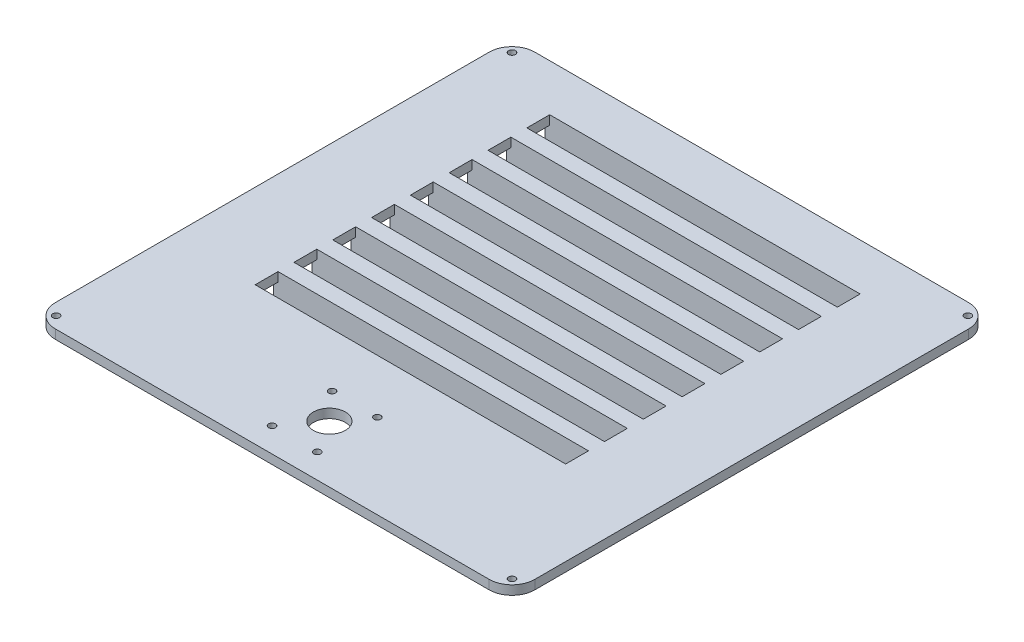
SolidWorks part; units mm, degrees
ref_plane "Front Plane" through (0, 0, 0) normal (0, 0, 1) x (1, 0, 0)
ref_plane "Top Plane" through (0, 0, 0) normal (0, 1, 0) x (1, 0, 0)
ref_plane "Right Plane" through (0, 0, 0) normal (1, 0, 0) x (0, 0, -1)
sketch "Sketch1" plane through (0, 0, 0) normal (0, 1, 0) x (1, 0, 0)
  line L0 (-101, -101) -> (-101, 101)
  line L5 (-105, -105) -> (105, -105)
  line L6 (-105, -105) -> (-105, 105)
  line L7 (-105, 105) -> (105, 105)
  line L8 (105, -105) -> (105, 105)
  line L9 (-101, 101) -> (101, 101)
  line L10 (101, -101) -> (101, 101)
  line L11 (-101, -101) -> (101, -101)
  line L12 (-101, 101) -> (-99.8333, 99.8333) construction
  line L13 (-55, 0) -> (55, 0) construction
  line L14 (-101, -101) -> (-99.8333, -99.8333) construction
  line L15 (0, -55) -> (0, 55) construction
  line L16 (101, -101) -> (99.8333, -99.8333) construction
  line L17 (101, 101) -> (99.8333, 99.8333) construction
  circle A1 centre (-99.8333, 99.8333) radius 1.5
  circle A2 centre (-99.8333, -99.8333) radius 1.5
  circle A3 centre (99.8333, -99.8333) radius 1.5
  circle A4 centre (99.8333, 99.8333) radius 1.5
  point P0 (0, 0)
  point P6 (-105, 0)
  point P7 (0, 105)
  dimension "D3" = 4
  dimension "D4" = 3
  dimension "D1" = 210
  dimension "D2" = 210
  dimension "D5" = 1.65
  dimension "D6" = 45
extrude "MainExtrude" add sketch "Sketch1" along normal blind 4 contours L6 L5 L8 L7
extrude "ScrewHoles" cut sketch "Sketch1<6>" along normal up to surface (4 mm away) contours A1 | A2 | A3 | A4 up to face at (0, 4, 0)
sketch "Sketch1<6>" plane through (0, 0, 0) normal (0, 1, 0) x (1, 0, 0) same geometry as "Sketch1"
fillet "RoundedCorners" radius 10 4 edges at (-105, 2, -105) (-105, 2, 105) (105, 2, -105) (105, 2, 105)
sketch "Sketch3" plane through (0, 0, 0) normal (0, 1, 0) x (1, 0, 0)
  line L145 (-68, 96.5) -> (68, 96.5) construction
  line L146 (-68, 96.5) -> (-68, -56.5) construction
  line L147 (-68, -56.5) -> (68, -56.5) construction
  line L148 (68, 96.5) -> (68, -56.5) construction
  line L149 (-68, 96.5) -> (68, -56.5) construction
  line L151 (68, 96.5) -> (-68, -56.5) construction
  line L152 (-68, 79.5) -> (68, 79.5) construction
  line L154 (-68, 62.5) -> (68, 62.5) construction
  line L155 (-68, 45.5) -> (68, 45.5) construction
  line L157 (-68, 28.5) -> (68, 28.5) construction
  line L158 (-68, 11.5) -> (68, 11.5) construction
  line L159 (-68, -5.5) -> (68, -5.5) construction
  line L160 (-68, -22.5) -> (68, -22.5) construction
  line L161 (-68, -39.5) -> (68, -39.5) construction
  line L162 (-68, 74.5) -> (68, 74.5)
  line L163 (-68, 57.5) -> (68, 57.5)
  line L164 (-68, 40.5) -> (68, 40.5)
  line L165 (-68, 23.5) -> (68, 23.5)
  line L166 (-68, 6.5) -> (68, 6.5)
  line L167 (-68, -10.5) -> (68, -10.5)
  line L168 (-68, -27.5) -> (68, -27.5)
  line L169 (-68, -44.5) -> (68, -44.5)
  line L170 (-68, 84.5) -> (68, 84.5)
  line L171 (-68, 67.5) -> (68, 67.5)
  line L172 (-68, 50.5) -> (68, 50.5)
  line L173 (-68, 33.5) -> (68, 33.5)
  line L174 (-68, 16.5) -> (68, 16.5)
  line L175 (-68, -0.5) -> (68, -0.5)
  line L176 (-68, -17.5) -> (68, -17.5)
  line L177 (-68, -34.5) -> (68, -34.5)
  line L178 (-68, 74.5) -> (-68, 84.5)
  line L179 (68, 74.5) -> (68, 84.5)
  line L180 (-68, 57.5) -> (-68, 67.5)
  line L181 (68, 57.5) -> (68, 67.5)
  line L182 (-68, 40.5) -> (-68, 50.5)
  line L183 (68, 40.5) -> (68, 50.5)
  line L184 (-68, 23.5) -> (-68, 33.5)
  line L185 (68, 23.5) -> (68, 33.5)
  line L186 (-68, 6.5) -> (-68, 16.5)
  line L187 (68, 6.5) -> (68, 16.5)
  line L188 (-68, -10.5) -> (-68, -0.5)
  line L189 (68, -10.5) -> (68, -0.5)
  line L190 (-68, -27.5) -> (-68, -17.5)
  line L191 (68, -27.5) -> (68, -17.5)
  line L192 (-68, -44.5) -> (-68, -34.5)
  line L193 (68, -44.5) -> (68, -34.5)
  line L200 (-10.8, -68) -> (-10.8, -94.3) construction
  line L201 (-95, -105) -> (95, -105) construction
  line L207 (-97.2358, 20) -> (95.5763, 20) construction
  line L208 (-10.8, -68) -> (9, -68) construction
  circle A0 centre (0, -80) radius 7
  circle A1 centre (-10.8, -68) radius 1.5
  circle A2 centre (-10.8, -94.3) radius 1.5
  circle A3 centre (9, -94.3) radius 1.5
  circle A4 centre (9, -68) radius 1.5
  point P70 (0, 20)
  dimension "D18" = 14
  dimension "D19" = 25
  dimension "D21" = 35.5
  dimension "D25" = 3
  dimension "D26" = 3
  dimension "D27" = 19.8
  dimension "D15" = 10.8
  dimension "D16" = 12
  dimension "D1" = 136
  dimension "D2" = 153
  dimension "D3" = 17
  dimension "D4" = 17
  dimension "D5" = 17
  dimension "D6" = 17
  dimension "D7" = 17
  dimension "D8" = 17
  dimension "D9" = 17
  dimension "D11" = 17
  dimension "D13" = 5
  dimension "D14" = 129
  dimension "D10" = 17
  dimension "D12" = 5
  dimension "D17" = 9
  dimension "D20" = 20
  dimension "D22" = 14.3
  dimension "D28" = 26.3
extrude "Trench" cut sketch "Sketch3" along normal blind 10
sketch "Sketch4" plane through (0, 0, 0) normal (0, 1, 0) x (1, 0, 0)
  line L0 (68, -34.5) -> (68, -44.5) construction
  line L1 (68, -44.5) -> (-68, -44.5) construction
  line L2 (-68, -44.5) -> (-68, -34.5) construction
  line L3 (-68, -34.5) -> (68, -34.5) construction
  line L4 (68, -17.5) -> (68, -27.5) construction
  line L5 (68, -27.5) -> (-68, -27.5) construction
  line L6 (-68, -27.5) -> (-68, -17.5) construction
  line L7 (-68, -17.5) -> (68, -17.5) construction
  line L8 (68, -0.5) -> (68, -10.5) construction
  line L9 (68, -10.5) -> (-68, -10.5) construction
  line L10 (-68, -10.5) -> (-68, -0.5) construction
  line L11 (-68, -0.5) -> (68, -0.5) construction
  line L12 (68, 16.5) -> (68, 6.5) construction
  line L13 (68, 6.5) -> (-68, 6.5) construction
  line L14 (-68, 6.5) -> (-68, 16.5) construction
  line L15 (-68, 16.5) -> (68, 16.5) construction
  line L16 (68, 33.5) -> (68, 23.5) construction
  line L17 (68, 23.5) -> (-68, 23.5) construction
  line L18 (-68, 23.5) -> (-68, 33.5) construction
  line L19 (-68, 33.5) -> (68, 33.5) construction
  line L20 (68, 50.5) -> (68, 40.5) construction
  line L21 (68, 40.5) -> (-68, 40.5) construction
  line L22 (-68, 40.5) -> (-68, 50.5) construction
  line L23 (-68, 50.5) -> (68, 50.5) construction
  line L24 (68, 67.5) -> (68, 57.5) construction
  line L25 (68, 57.5) -> (-68, 57.5) construction
  line L26 (-68, 57.5) -> (-68, 67.5) construction
  line L27 (-68, 67.5) -> (68, 67.5) construction
  line L28 (68, 84.5) -> (68, 74.5) construction
  line L29 (68, 74.5) -> (-68, 74.5) construction
  line L30 (-68, 74.5) -> (-68, 84.5) construction
  line L31 (-68, 84.5) -> (68, 84.5) construction
  line L32 (68, -34.5) -> (68, -44.5)
  line L33 (68, -44.5) -> (-68, -44.5)
  line L34 (-68, -44.5) -> (-68, -34.5)
  line L35 (-68, -34.5) -> (68, -34.5)
  line L36 (68, -17.5) -> (68, -27.5)
  line L37 (68, -27.5) -> (-68, -27.5)
  line L38 (-68, -27.5) -> (-68, -17.5)
  line L39 (-68, -17.5) -> (68, -17.5)
  line L40 (68, -0.5) -> (68, -10.5)
  line L41 (68, -10.5) -> (-68, -10.5)
  line L42 (-68, -10.5) -> (-68, -0.5)
  line L43 (-68, -0.5) -> (68, -0.5)
  line L44 (68, 16.5) -> (68, 6.5)
  line L45 (68, 6.5) -> (-68, 6.5)
  line L46 (-68, 6.5) -> (-68, 16.5)
  line L47 (-68, 16.5) -> (68, 16.5)
  line L48 (68, 33.5) -> (68, 23.5)
  line L49 (68, 23.5) -> (-68, 23.5)
  line L50 (-68, 23.5) -> (-68, 33.5)
  line L51 (-68, 33.5) -> (68, 33.5)
  line L52 (68, 50.5) -> (68, 40.5)
  line L53 (68, 40.5) -> (-68, 40.5)
  line L54 (-68, 40.5) -> (-68, 50.5)
  line L55 (-68, 50.5) -> (68, 50.5)
  line L56 (68, 67.5) -> (68, 57.5)
  line L57 (68, 57.5) -> (-68, 57.5)
  line L58 (-68, 57.5) -> (-68, 67.5)
  line L59 (-68, 67.5) -> (68, 67.5)
  line L60 (68, 84.5) -> (68, 74.5)
  line L61 (68, 74.5) -> (-68, 74.5)
  line L62 (-68, 74.5) -> (-68, 84.5)
  line L63 (-68, 84.5) -> (68, 84.5)
  line L64 (70, 86.5) -> (70, 72.5)
  line L65 (70, 72.5) -> (-70, 72.5)
  line L66 (-70, 72.5) -> (-70, 86.5)
  line L67 (-70, 86.5) -> (70, 86.5)
  line L68 (70, 69.5) -> (70, 55.5)
  line L69 (70, 55.5) -> (-70, 55.5)
  line L70 (-70, 55.5) -> (-70, 69.5)
  line L71 (-70, 69.5) -> (70, 69.5)
  line L72 (70, 52.5) -> (70, 38.5)
  line L73 (70, 38.5) -> (-70, 38.5)
  line L74 (-70, 38.5) -> (-70, 52.5)
  line L75 (-70, 52.5) -> (70, 52.5)
  line L76 (70, 35.5) -> (70, 21.5)
  line L77 (70, 21.5) -> (-70, 21.5)
  line L78 (-70, 21.5) -> (-70, 35.5)
  line L79 (-70, 35.5) -> (70, 35.5)
  line L80 (70, 18.5) -> (70, 4.5)
  line L81 (70, 4.5) -> (-70, 4.5)
  line L82 (-70, 4.5) -> (-70, 18.5)
  line L83 (-70, 18.5) -> (70, 18.5)
  line L84 (70, 1.5) -> (70, -12.5)
  line L85 (70, -12.5) -> (-70, -12.5)
  line L86 (-70, -12.5) -> (-70, 1.5)
  line L87 (-70, 1.5) -> (70, 1.5)
  line L88 (70, -15.5) -> (70, -29.5)
  line L89 (70, -29.5) -> (-70, -29.5)
  line L90 (-70, -29.5) -> (-70, -15.5)
  line L91 (-70, -15.5) -> (70, -15.5)
  line L92 (70, -32.5) -> (70, -46.5)
  line L93 (70, -46.5) -> (-70, -46.5)
  line L94 (-70, -46.5) -> (-70, -32.5)
  line L95 (-70, -32.5) -> (70, -32.5)
  dimension "D1" = 2
extrude "Trench Walls" add sketch "Sketch4" against normal blind 4
sketch "Sketch5" plane through (0, -4, 0) normal (0, -1, 0) x (1, 0, 0)
  line L0 (-70, -86.5) -> (70, -86.5) construction
  line L1 (70, -86.5) -> (70, -72.5) construction
  line L2 (70, -72.5) -> (-70, -72.5) construction
  line L3 (-70, -72.5) -> (-70, -86.5) construction
  line L4 (-70, -69.5) -> (70, -69.5) construction
  line L5 (70, -69.5) -> (70, -55.5) construction
  line L6 (70, -55.5) -> (-70, -55.5) construction
  line L7 (-70, -55.5) -> (-70, -69.5) construction
  line L8 (-70, -52.5) -> (70, -52.5) construction
  line L9 (70, -52.5) -> (70, -38.5) construction
  line L10 (70, -38.5) -> (-70, -38.5) construction
  line L11 (-70, -38.5) -> (-70, -52.5) construction
  line L12 (-70, -35.5) -> (70, -35.5) construction
  line L13 (70, -35.5) -> (70, -21.5) construction
  line L14 (70, -21.5) -> (-70, -21.5) construction
  line L15 (-70, -21.5) -> (-70, -35.5) construction
  line L16 (-70, -18.5) -> (70, -18.5) construction
  line L17 (70, -18.5) -> (70, -4.5) construction
  line L18 (70, -4.5) -> (-70, -4.5) construction
  line L19 (-70, -4.5) -> (-70, -18.5) construction
  line L20 (-70, -1.5) -> (70, -1.5) construction
  line L21 (70, -1.5) -> (70, 12.5) construction
  line L22 (70, 12.5) -> (-70, 12.5) construction
  line L23 (-70, 12.5) -> (-70, -1.5) construction
  line L24 (-70, 15.5) -> (70, 15.5) construction
  line L25 (70, 15.5) -> (70, 29.5) construction
  line L26 (70, 29.5) -> (-70, 29.5) construction
  line L27 (-70, 29.5) -> (-70, 15.5) construction
  line L28 (-70, 32.5) -> (70, 32.5) construction
  line L29 (70, 32.5) -> (70, 46.5) construction
  line L30 (70, 46.5) -> (-70, 46.5) construction
  line L31 (-70, 46.5) -> (-70, 32.5) construction
  line L32 (-70, -86.5) -> (70, -86.5)
  line L33 (70, -86.5) -> (70, -72.5)
  line L34 (70, -72.5) -> (-70, -72.5)
  line L35 (-70, -72.5) -> (-70, -86.5)
  line L36 (-70, -69.5) -> (70, -69.5)
  line L37 (70, -69.5) -> (70, -55.5)
  line L38 (70, -55.5) -> (-70, -55.5)
  line L39 (-70, -55.5) -> (-70, -69.5)
  line L40 (-70, -52.5) -> (70, -52.5)
  line L41 (70, -52.5) -> (70, -38.5)
  line L42 (70, -38.5) -> (-70, -38.5)
  line L43 (-70, -38.5) -> (-70, -52.5)
  line L44 (-70, -35.5) -> (70, -35.5)
  line L45 (70, -35.5) -> (70, -21.5)
  line L46 (70, -21.5) -> (-70, -21.5)
  line L47 (-70, -21.5) -> (-70, -35.5)
  line L48 (-70, -18.5) -> (70, -18.5)
  line L49 (70, -18.5) -> (70, -4.5)
  line L50 (70, -4.5) -> (-70, -4.5)
  line L51 (-70, -4.5) -> (-70, -18.5)
  line L52 (-70, -1.5) -> (70, -1.5)
  line L53 (70, -1.5) -> (70, 12.5)
  line L54 (70, 12.5) -> (-70, 12.5)
  line L55 (-70, 12.5) -> (-70, -1.5)
  line L56 (-70, 15.5) -> (70, 15.5)
  line L57 (70, 15.5) -> (70, 29.5)
  line L58 (70, 29.5) -> (-70, 29.5)
  line L59 (-70, 29.5) -> (-70, 15.5)
  line L60 (-70, 32.5) -> (70, 32.5)
  line L61 (70, 32.5) -> (70, 46.5)
  line L62 (70, 46.5) -> (-70, 46.5)
  line L63 (-70, 46.5) -> (-70, 32.5)
extrude "Trench Bottom" add sketch "Sketch5" along normal blind 2
sketch "Sketch7" plane through (70, 0, 0) normal (1, 0, 0) x (0, 0, -1)
  line L1 (-44.5, 0) -> (-34.5, 0)
  line L2 (-44.5, 0) -> (-44.5, -6)
  line L3 (-44.5, -6) -> (-34.5, -6)
  line L4 (-34.5, 0) -> (-34.5, -6)
  line L5 (-46.5, -6) -> (-46.5, 0) construction
  line L6 (-32.5, -6) -> (-46.5, -6) construction
  line L7 (-27.5, 0) -> (-27.5, -6)
  line L8 (-27.5, 0) -> (-17.5, 0)
  line L9 (-17.5, 0) -> (-17.5, -6)
  line L10 (-27.5, -6) -> (-17.5, -6)
  line L11 (-10.5, 0) -> (-10.5, -6)
  line L12 (-10.5, 0) -> (-0.5, 0)
  line L13 (-0.5, 0) -> (-0.5, -6)
  line L14 (-10.5, -6) -> (-0.5, -6)
  line L15 (6.5, 0) -> (6.5, -6)
  line L16 (6.5, 0) -> (16.5, 0)
  line L17 (16.5, 0) -> (16.5, -6)
  line L18 (6.5, -6) -> (16.5, -6)
  line L19 (23.5, 0) -> (23.5, -6)
  line L20 (23.5, 0) -> (33.5, 0)
  line L21 (33.5, 0) -> (33.5, -6)
  line L22 (23.5, -6) -> (33.5, -6)
  line L23 (40.5, 0) -> (40.5, -6)
  line L24 (40.5, 0) -> (50.5, 0)
  line L25 (50.5, 0) -> (50.5, -6)
  line L26 (40.5, -6) -> (50.5, -6)
  line L27 (57.5, 0) -> (57.5, -6)
  line L28 (57.5, 0) -> (67.5, 0)
  line L29 (67.5, 0) -> (67.5, -6)
  line L30 (57.5, -6) -> (67.5, -6)
  line L31 (74.5, 0) -> (74.5, -6)
  line L32 (74.5, 0) -> (84.5, 0)
  line L33 (84.5, 0) -> (84.5, -6)
  line L34 (74.5, -6) -> (84.5, -6)
  line L35 (-29.5, -6) -> (-29.5, 0) construction
  line L36 (-46.5, 0) -> (-32.5, 0) construction
  dimension "D3" = 10
  dimension "D4" = 2
  dimension "D5" = 8
  dimension "D6" = 2
extrude "Wire Opening" cut sketch "Sketch7" against normal through all both and the other way through all
sketch "Sketch9" plane through (0, 0, 0) normal (0, -1, 0) x (1, 0, 0)
  line L0 (-95, 105) -> (95, 105) construction
  line L1 (-70, 46.5) -> (70, 46.5) construction
  line L5 (-105, 95) -> (-105, -95) construction
  circle A0 centre (-94, 92) radius 0.98
  circle A1 centre (-94, 92) radius 2
  circle A2 centre (-19.73, 92) radius 2
  circle A3 centre (-19.73, 92) radius 0.98
  circle A4 centre (-94, 56.16) radius 2
  circle A5 centre (-94, 56.16) radius 0.98
  circle A6 centre (-19.73, 56.16) radius 0.98
  circle A7 centre (-19.73, 56.16) radius 2
  circle A8 centre (-99.8333, 99.8333) radius 1.5 construction
  dimension "D1" = 13
  dimension "D2" = 35.84
  dimension "D5" = 1.96
  dimension "D6" = 4
  dimension "D7" = 1.96
  dimension "D8" = 4
  dimension "D3" = 11
  dimension "D4" = 74.27
  dimension "D9" = 9.7666
  dimension "D10" = 9.66
extrude "PCB Holes" add sketch "Sketch9" along normal blind 4
fillet "PCB Rounds" radius 2 4 edges at (-19.73, 0, 58.16) (-19.73, 0, 94) (-94, 0, 58.16) (-94, 0, 94)
equation "\"1_LED\"= 17mm"
equation "\"2_LED\"= \"1_LED\" * 2"
equation "\"3_LED\"= \"1_LED\" * 3"
equation "\"4_LED\"= \"1_LED\" * 4"
equation "\"5_LED\"= \"1_LED\" * 5"
equation "\"6_LED\"= \"1_LED\" * 6"
equation "\"7_LED\"= \"1_LED\" * 7"
equation "\"8_LED\"= \"1_LED\" * 8"
equation "\"9_LED\"= \"1_LED\" * 9"
equation "\"10_LED\"= \"1_LED\" * 10"
equation "\"11_LED\"= \"1_LED\" * 11"
equation "\"12_LED\"= \"1_LED\" * 12"
